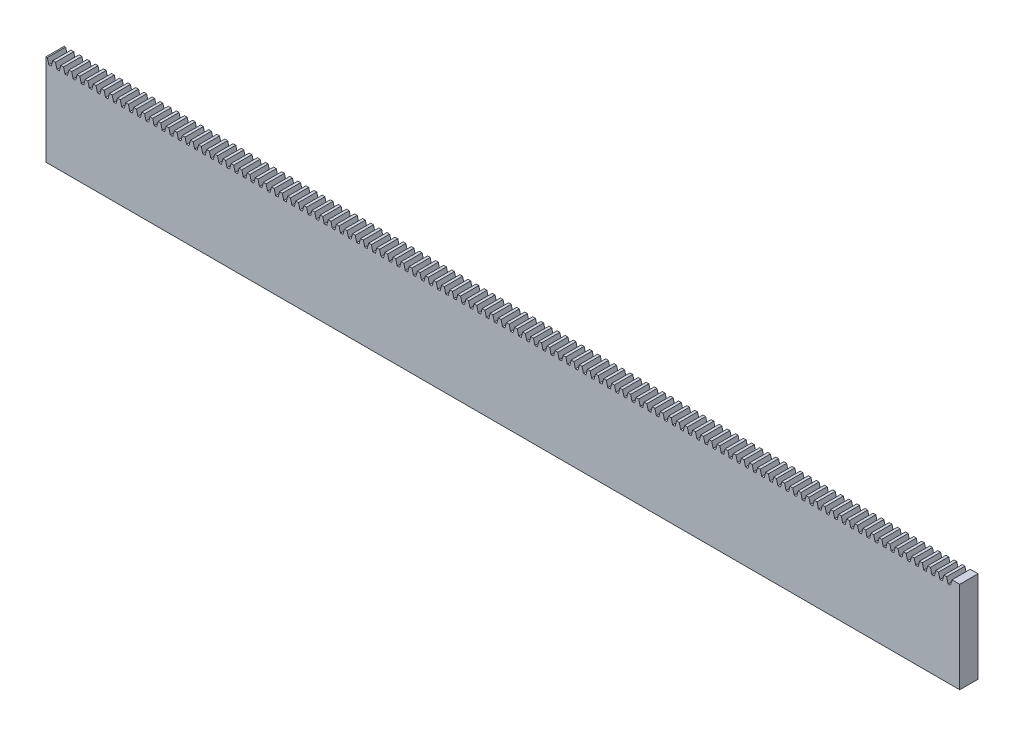
SolidWorks part; units mm, degrees
material "Brass"
ref_plane "Front Plane" through (0, 0, 0) normal (0, 0, 1) x (1, 0, 0)
ref_plane "Top Plane" through (0, 0, 0) normal (0, 1, 0) x (1, 0, 0)
ref_plane "Right Plane" through (0, 0, 0) normal (1, 0, 0) x (0, 0, -1)
sketch "Sketch1" plane through (0, 0, 0) normal (0, 0, 1) x (1, 0, 0)
  line L0 (0, 0) -> (300, 0)
  line L1 (300, 0) -> (300, 30)
  line L2 (300, 30) -> (0, 30)
  line L3 (0, 30) -> (0, 0)
  dimension "D1" = 300
  dimension "D2" = 30
extrude "Boss-Extrude1" add sketch "Sketch1" along normal blind 6
sketch "Sketch2" plane through (0, 0, 0) normal (0, 0, 1) x (1, 0, 0)
  line L0 (0.9183, 28.1737) -> (0.1874, 31)
  line L1 (0.1874, 31) -> (2.4725, 31)
  line L2 (2.4725, 31) -> (1.7416, 28.1737)
  line L3 (1.7416, 28.1737) -> (0.9183, 28.1737)
extrude "Cut-Extrude2" cut sketch "Sketch2" against normal blind 7 and the other way blind 7
pattern_linear "LPattern1" count 112 spacing 2.6599 along (1, 0, 0) of "Cut-Extrude2"
